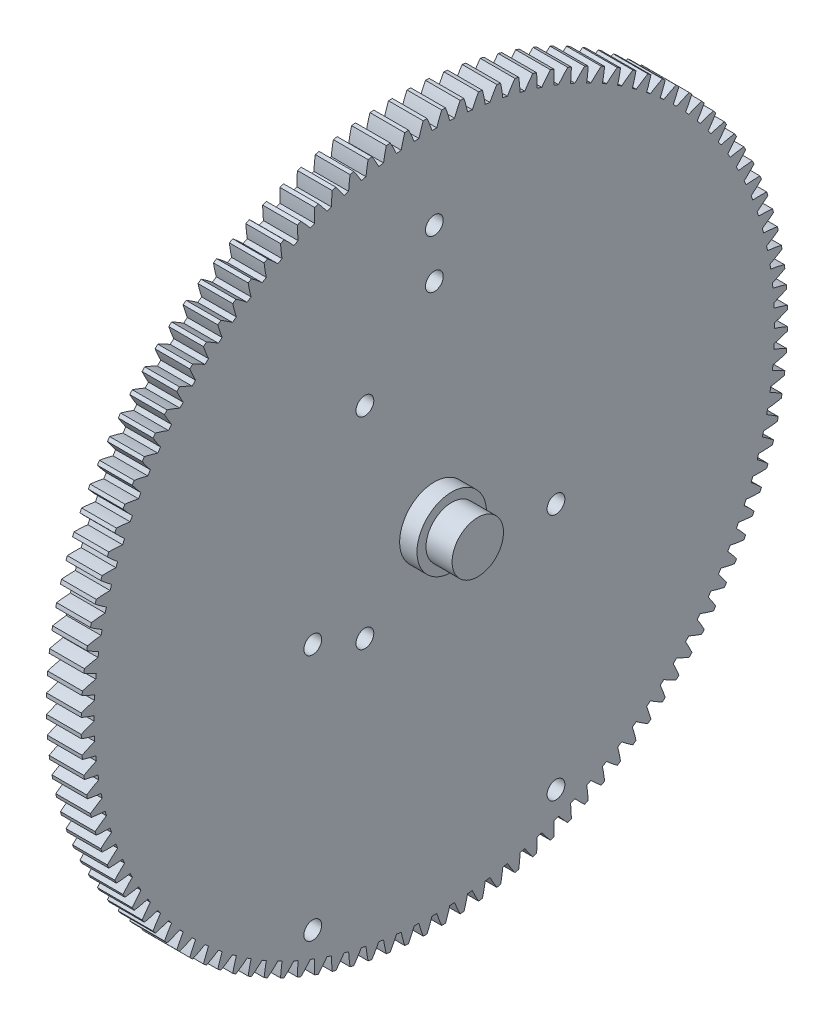
SolidWorks part; units mm, degrees
ref_plane "Plane1" through (0, 0, 0) normal (0, 0, 1) x (1, 0, 0)
ref_plane "Plane2" through (0, 0, 0) normal (0, 1, 0) x (1, 0, 0)
ref_plane "Plane3" through (0, 0, 0) normal (1, 0, 0) x (0, 0, -1)
other "Configuration Table"
sketch "HoldingSke" plane through (0, 0, 0) normal (0, 1, 0) x (1, 0, 0)
  line L0 (0, 0) -> (-152.4, -263.9645)
  line L1 (-15, 0) -> (100, 0) construction
  line L2 (0, 0) -> (-2.1039, 2.3779)
  line L3 (0, 0) -> (-11.863, 4.5341)
  line L4 (0, 0) -> (-4.318, 7.479)
  line L5 (0, 0) -> (-47.5972, -17.7524)
  line L6 (0, 0) -> (-10.5278, -7.1032)
  line L7 (-2.1039, 2.3779) -> (8.8308, 51.9871)
  line L8 (-76.2, 54.61) -> (-54.9402, 54.61)
  line L9 (-71.009, 38.7566) -> (-53.1078, 45.2721)
  line L10 (-76.2, 71.12) -> (104.1128, 71.12)
  line L11 (0, 0) -> (-12.7, 0)
  line L12 (-76.2, 101.6) -> (-76.1147, 101.6)
  line L13 (24.9733, 27.94) -> (52.9518, 28.4284)
  line L14 (24.9733, 27.94) -> (24.9746, 27.94)
  line L15 (24.9733, 27.94) -> (100.4006, 29.5858)
  circle A0 centre (0, 0) radius 9.525
  circle A1 centre (0, 0) radius 38.1
  circle A2 centre (0, 0) radius 38.1
  circle A3 centre (0, 0) radius 9.525
  dimension "MHD" = 76.2
  dimension "Hub_dia" = 76.2
  dimension "Bore" = 19.05
  dimension "MBD" = 19.05
  dimension "Num_teeth" = 120
  dimension "Pitch" = 304.8
  dimension "Overall_len" = 50.8
  dimension "Show_teeth" = 120
  dimension "Thickness" = 12.7
  dimension "OAL" = 50.8001
  dimension "T_dim" = 21.2598
  dimension "Ap" = 20
  dimension "H" = 19.05
  dimension "Pitch_radius" = 180.3128
  dimension "Width" = 12.7
  dimension "Backlash" = 0.0853
  dimension "Addendum_fac" = 1
  dimension "Dedendum_fac" = 1.25
  dimension "Clearance_fac" = 0.25
  dimension "Dedendum_add" = 0.0013
sketch "BasProSke" plane through (0, 0, 0) normal (0, 1, 0) x (1, 0, 0)
  line L0 (-10, 0) -> (60, 0) construction
  line L1 (0, 0) -> (0, 129.1167)
  line L2 (0, 0) -> (12.7, 0)
  line L3 (12.7, 0) -> (12.7, 129.1167)
  line L4 (12.7, 129.1167) -> (0, 129.1167)
  dimension "Thickness" = 12.7
  dimension "Diameter" = 258.2333
revolve "Base-Revolve" add sketch "BasProSke" angle 360 about L0
sketch "TooCutSke" plane through (0, 0, 0) normal (1, 0, 0) x (0, 0, -1)
  line L1 (0, 0) -> (0, 107) construction
  line L2 (0, 0) -> (-1.8117, 126.9871) construction
  line L3 (0, 0) -> (-6.6485, 253.8949) construction
  line L4 (-1.8117, 126.9871) -> (-3.3242, 126.9475) construction
  arc A0 (0.878, 124.3498) -> (-0.878, 124.3498) centre (0, 0) ccw
  arc A1 (2.6872, 129.1141) -> (-2.6872, 129.1141) centre (0, 0) ccw
  circle A2 centre (0, 0) radius 127 construction
  circle A3 centre (0, 0) radius 119.341 construction
  arc A4 (-0.878, 124.3498) -> (-2.6872, 129.1141) centre (-49.2141, 108.7209) ccw
  arc A5 (2.6872, 129.1141) -> (0.878, 124.3498) centre (49.2141, 108.7209) ccw
  dimension "Root_dia" = 248.7058
  dimension "Overcut_dia" = 258.2841
  dimension "Pitch_dia" = 254
  dimension "Base_dia" = 238.6819
  dimension "Flank_rad" = 50.8
  dimension "Half_ang" = 1.5
  dimension "Half_CT" = 1.513
extrude "ToothCut" cut sketch "TooCutSke" along normal through all
fillet "Breaks" [suppressed] radius 0.0423 tangent propagation no
fillet "RootFillets" [suppressed] radius 0.5304
pattern_circular "TeethCuts" count 120 every 3 about axis through (-10, 0, 0) along (1, 0, 0) of "ToothCut", "RootFillets", "Breaks"
sketch "HubNeaOneSke" plane through (0, 0, 0) normal (-1, 0, 0) x (0, 0, 1)
  circle A0 centre (0, 0) radius 38.1
  dimension "Diameter" = 76.2
extrude "HubNearOne" [suppressed] add sketch "HubNeaOneSke" along normal blind 38.1001
sketch "HubNeaBotSke" plane through (0, 0, 0) normal (-1, 0, 0) x (0, 0, 1)
  circle A0 centre (0, 0) radius 38.1
  dimension "Diameter" = 76.2
extrude "HubNearBoth" [suppressed] add sketch "HubNeaBotSke" along normal blind 19.05
ref_plane "FarPln" through (12.7, 0, 0) normal (1, 0, 0) x (0, 0, -1)
sketch "HubFarSke" plane through (12.7, 0, 0) normal (1, 0, 0) x (0, 0, -1)
  circle A0 centre (0, 0) radius 38.1
  dimension "Diameter" = 76.2
extrude "HubFar" [suppressed] add sketch "HubFarSke" along normal blind 19.05
sketch "BorSke" plane through (0, 0, 0) normal (1, 0, 0) x (0, 0, -1)
  circle A0 centre (0, 0) radius 9.525
  dimension "Diameter" = 19.05
extrude "Bore" [suppressed] cut sketch "BorSke" along normal mid plane 101.6001
sketch "KeySke" plane through (0, 0, 0) normal (1, 0, 0) x (0, 0, -1)
  line L0 (-2.3813, 0) -> (-2.3813, 11.7348)
  line L1 (-2.3813, 11.7348) -> (2.3813, 11.7348)
  line L2 (2.3813, 11.7348) -> (2.3813, 0)
  line L3 (0, 0) -> (0, 34) construction
  line L4 (-2.3813, 0) -> (2.3813, 0)
  dimension "Offset" = 11.7348
  dimension "Width" = 4.7625
extrude "Keyway" [suppressed] cut sketch "KeySke" along normal mid plane 101.6001
pattern_circular "Keyway2" [suppressed] count 2 every 90 about axis through (-10, 0, 0) along (1, 0, 0)
sketch "Sketch1" plane through (0, 0, 0) normal (-1, 0, 0) x (0, 0, 1)
  line L0 (0, 12.7) -> (44.585, 12.7) construction
  line L1 (0, 12.7) -> (0, -76.4863) construction
  circle A2 centre (25.4, 49.53) radius 3.2512
  circle A3 centre (25.4, -24.13) radius 3.2512
  circle A4 centre (0, 93.98) radius 3.2512
  circle A5 centre (0, 76.2) radius 3.2512
  circle A6 centre (44.45, -16.51) radius 3.2512
  circle A7 centre (44.45, -106.934) radius 3.2512
  circle A8 centre (-44.45, -106.934) radius 3.2512
  circle A9 centre (-44.45, -16.51) radius 3.2512
  point P9 (0, 0)
  dimension "D1" = 6.5024
  dimension "D2" = 6.5024
  dimension "D6" = 6.5024
  dimension "D7" = 6.5024
  dimension "D10" = 6.5024
  dimension "D11" = 6.5024
  dimension "D3" = 17.78
  dimension "D4" = 73.66
  dimension "D5" = 25.4
  dimension "D8" = 76.2
  dimension "D9" = 73.66
  dimension "D12" = 90.424
  dimension "D13" = 44.45
  dimension "D14" = 16.51
  dimension "D15" = 12.7
extrude "Cut-Extrude1" cut sketch "Sketch1" against normal through all
sketch "Sketch2" plane through (12.7, 0, 0) normal (1, 0, 0) x (0, 0, -1)
  circle A0 centre (0, 0) radius 12.7
  dimension "D1" = 25.4
extrude "Boss-Extrude1" add sketch "Sketch2" along normal blind 6.35
sketch "Sketch3" plane through (19.05, 0, 0) normal (1, 0, 0) x (0, 0, -1)
  circle A0 centre (0, 0) radius 9.398
  dimension "D1" = 18.796
extrude "Boss-Extrude2" add sketch "Sketch3" along normal blind 9.525
equation "' \"Pitch@HoldingSke\" = 4"
equation "' \"Num_teeth@HoldingSke\" = 12"
equation "' \"Ap@HoldingSke\" =  20"
equation "' \"Ap@HoldingSke\" = 20"
equation "' \"Width@HoldingSke\" = 0.5"
equation "' \"Hub_dia@HoldingSke\"= 1"
equation "' \"Hub_dia@HoldingSke\" = 1"
equation "' \"Overall_len@HoldingSke\" = 1.0"
equation "' \"Bore@HoldingSke\" = 0.75"
equation "' \"T_dim@HoldingSke\" = 0.85"
equation "' \"Width@KeySke\" = 0.25"
equation "' \"Show_teeth@HoldingSke\" = 13"
equation "' \"Backlash@HoldingSke\" = 0.009"
equation "' \"Addendum_fac@HoldingSke\" = 1.0"
equation "' \"Dedendum_fac@HoldingSke\" = 1.25"
equation "' \"Dedendum_add@HoldingSke\" = 0.00005"
equation "' \"Clearance_fac@HoldingSke\" = 0.25"
equation "' \"Pitch@HoldingSke\" = 0.5"
equation "' \"Num_teeth@HoldingSke\" = 23"
equation "' \"Show_teeth@HoldingSke\" = 23"
equation "' \"Backlash@HoldingSke\" = 0.0375"
equation "\"Overcut_dia@TooCutSke\" = (\"Num_teeth@HoldingSke\" + 2 * \"Addendum_fac@HoldingSke\") / \"Pitch@HoldingSke\" + 0.002"
equation "\"Pitch_dia@TooCutSke\" = \"Num_teeth@HoldingSke\" / \"Pitch@HoldingSke\""
equation "\"Base_dia@TooCutSke\" = \"Num_teeth@HoldingSke\" / \"Pitch@HoldingSke\" * cos((\"Ap@HoldingSke\"  * 3.14159265 / 180))"
equation "\"Root_dia@TooCutSke\" = (\"Num_teeth@HoldingSke\" + 2) / \"Pitch@HoldingSke\" - 2 * (\"Addendum_fac@HoldingSke\" + \"Dedendum_fac@HoldingSke\") / \"Pitch@HoldingSke\" - \"Dedendum_add@HoldingSke\" * 2"
equation "\"Half_ang@TooCutSke\" = 180 / \"Num_teeth@HoldingSke\""
equation "\"Half_CT@TooCutSke\" = \"Num_teeth@HoldingSke\" / \"Pitch@HoldingSke\" * sin((3.14159265 / 2 / \"Num_teeth@HoldingSke\")) / 2 - 7 * \"Backlash@HoldingSke\" / 4"
equation "\"Flank_rad@TooCutSke\" = \"Num_teeth@HoldingSke\" / \"Pitch@HoldingSke\" / 5"
equation "\"Radius@RootFillets\" = \"Clearance_fac@HoldingSke\" / \"Pitch@HoldingSke\" + \"Dedendum_add@HoldingSke\""
equation "\"Break_rad@Breaks\" = 0.02 / \"Pitch@HoldingSke\""
equation "\"Thickness@HoldingSke\" = \"Width@HoldingSke\""
equation "\"OAL@HoldingSke\" = \"Thickness@HoldingSke\""
equation "\"MHD@HoldingSke\" = (\"Num_teeth@HoldingSke\" + 2) / \"Pitch@HoldingSke\" - 2 * (\"Addendum_fac@HoldingSke\" + \"Dedendum_fac@HoldingSke\")  / \"Pitch@HoldingSke\" - \"Dedendum_add@HoldingSke\" * 2"
equation "\"MBD@HoldingSke\" = (\"Num_teeth@HoldingSke\" + 2) / \"Pitch@HoldingSke\" - 2 * (\"Addendum_fac@HoldingSke\" + \"Dedendum_fac@HoldingSke\")  / \"Pitch@HoldingSke\" - \"Dedendum_add@HoldingSke\" * 2 - 0.002"
equation "\"MHD@HoldingSke\" = ((sgn( \"MHD@HoldingSke\" - \"Hub_dia@HoldingSke\" )-1)*( \"MHD@HoldingSke\" - \"Hub_dia@HoldingSke\" ))/-2+ \"Hub_dia@HoldingSke\""
equation "\"MBD@HoldingSke\" = ((sgn( \"MBD@HoldingSke\" - \"Bore@HoldingSke\" )-1)*( \"MBD@HoldingSke\" - \"Bore@HoldingSke\" ))/-2+ \"Bore@HoldingSke\""
equation "\"OAL@HoldingSke\" = ((sgn( \"OAL@HoldingSke\" - \"Overall_len@HoldingSke\" )+1)*( \"OAL@HoldingSke\" - \"Overall_len@HoldingSke\" ))/2 + \"Overall_len@HoldingSke\" + 0.000002"
equation "\"Num_teeth@TeethCuts\" = int( \"Show_teeth@HoldingSke\" ) + 1"
equation "\"Num_teeth@TeethCuts\" = ((sgn( \"Num_teeth@TeethCuts\" - \"Num_teeth@HoldingSke\" )-1)*( \"Num_teeth@TeethCuts\" - \"Num_teeth@HoldingSke\" ))/-2+ \"Num_teeth@HoldingSke\""
equation "\"Num_teeth@TeethCuts\" = ((sgn( \"Num_teeth@TeethCuts\" - 2.0)+1)*( \"Num_teeth@TeethCuts\" - 2.0))/2 +2.0"
equation "\"Angle@TeethCuts\" = 360.0 / \"Num_teeth@HoldingSke\""
equation "\"Diameter@BasProSke\" = (\"Num_teeth@HoldingSke\" + 2 * \"Addendum_fac@HoldingSke\") / \"Pitch@HoldingSke\""
equation "\"Thickness@BasProSke\"  = \"Thickness@HoldingSke\""
equation "' \"Fillet_rad@BasProSke\" =  \"Thickness@HoldingSke\" * 0.05"
equation "' \"Fillet_rad@BasProSke\" = \"Thickness@HoldingSke\" * 0.05"
equation "\"MHD@HoldingSke\" = ((sgn( \"MHD@HoldingSke\" - \"Root_dia@TooCutSke\" )-1)*( \"MHD@HoldingSke\" - \"Root_dia@TooCutSke\" ))/-2+ \"Root_dia@TooCutSke\""
equation "\"Diameter@HubNeaOneSke\" = \"MHD@HoldingSke\""
equation "\"Length@HubNearOne\" = \"OAL@HoldingSke\" - \"Thickness@BasProSke\""
equation "\"Diameter@HubNeaBotSke\" = \"MHD@HoldingSke\""
equation "\"Length@HubNearBoth\" = ( \"OAL@HoldingSke\" - \"Thickness@BasProSke\" ) / 2.0"
equation "\"Thickness@FarPln\" = \"Thickness@BasProSke\""
equation "\"Diameter@HubFarSke\" = \"MHD@HoldingSke\""
equation "\"Length@HubFar\" = ( \"OAL@HoldingSke\" - \"Thickness@BasProSke\" ) / 2.0"
equation "\"Diameter@BorSke\" = \"MBD@HoldingSke\""
equation "\"D1@Bore\" = \"OAL@HoldingSke\" * 2.0"
equation "\"D1@Keyway\" = \"OAL@HoldingSke\" * 2.0"
equation "\"Offset@KeySke\" = \"T_dim@HoldingSke\" - \"MBD@HoldingSke\" / 2.0"
